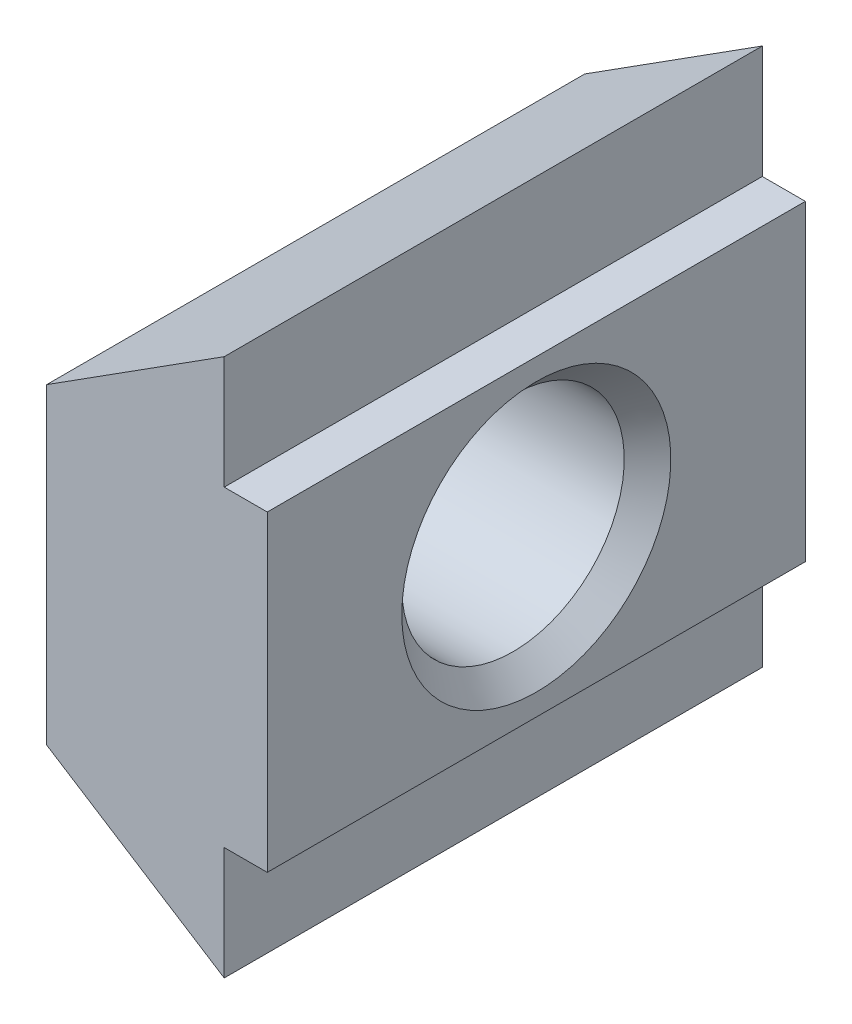
SolidWorks part; units mm, degrees
material "A6061"
ref_plane "前视基准面" through (0, 0, 0) normal (0, 0, 1) x (1, 0, 0)
ref_plane "上视基准面" through (0, 0, 0) normal (0, 1, 0) x (1, 0, 0)
ref_plane "右视基准面" through (0, 0, 0) normal (1, 0, 0) x (0, 0, -1)
sketch "草图1" plane through (0, 0, 0) normal (0, 0, 1) x (1, 0, 0)
  line L0 (-4.1, -2.9) -> (-0.8, -5)
  line L1 (-0.8, -5) -> (-0.8, -2.9)
  line L2 (-0.8, -2.9) -> (0, -2.9)
  line L3 (0, -2.9) -> (0, 2.9)
  line L4 (0, 2.9) -> (-0.8, 2.9)
  line L5 (-0.8, 2.9) -> (-0.8, 5)
  line L6 (-0.8, 5) -> (-4.1, 2.9)
  line L7 (-4.1, 2.9) -> (-4.1, -2.9)
extrude "凸台-拉伸1" add sketch "草图1" against normal blind 5 and the other way blind 5
sketch "草图2" plane through (0, 0, 0) normal (0, 0, 1) x (1, 0, 0)
  line L0 (-4.1, 0) -> (-4.1, 2.5)
  line L1 (-4.1, 2.5) -> (-3.667, 2.067)
  line L2 (-3.667, 2.067) -> (-0.433, 2.067)
  line L3 (-0.433, 2.067) -> (0, 2.5)
  line L4 (0, 2.5) -> (0, 0)
  line L5 (0, 0) -> (-4.1, 0)
  line L6 (0, 0) -> (-4.1, 0) construction
revolve "切除-旋转1" cut sketch "草图2" angle 360 about L6 reverse direction yes
cosmetic thread "装饰螺纹线1" parameters "D1"=4.1, "D2"=5
ref_plane "基准面1" through (-4.1, 0, 0) normal (1, 0, 0) x (0, 0, -1)
ref_plane "基准面2" through (-0.8, 0, 0) normal (1, 0, 0) x (0, 0, -1)
ref_plane "nut XY" through (0, 0, 0) normal (1, 0, 0) x (0, 0, -1)
ref_plane "nut XZ" through (0, 0, 0) normal (0, -1, 0) x (-1, 0, 0)
ref_plane "nut YZ" through (0, 0, 0) normal (0, 0, -1) x (-1, 0, 0)
ref_axis "nut X" through (0, 0, 80.9) along (0, 0, -1)
ref_axis "nut Y" through (0, -50, 0) along (0, 1, 0)
ref_axis "nut Z" through (80.9, 0, 0) along (-1, 0, 0)
sketch3d "nut"
  point P0 (0, 0, 0)
ref_plane "to_bolt XY" through (-4.1, 0, 0) normal (1, 0, 0) x (0, 0, -1)
ref_plane "to_bolt XZ" through (0, 0, 0) normal (0, -1, 0) x (-1, 0, 0)
ref_plane "to_bolt YZ" through (0, 0, 0) normal (0, 0, -1) x (-1, 0, 0)
ref_axis "to_bolt X" through (-4.1, 0, 80.9) along (0, 0, -1)
ref_axis "to_bolt Y" through (-4.1, -50, 0) along (0, 1, 0)
ref_axis "to_bolt Z" through (80.9, 0, 0) along (-1, 0, 0)
sketch3d "to_bolt"
  point P0 (-4.1, 0, 0)
ref_plane "to_frames XY" through (-0.8, 0, 0) normal (1, 0, 0) x (0, 0, -1)
ref_plane "to_frames XZ" through (0, 0, 0) normal (0, -1, 0) x (-1, 0, 0)
ref_plane "to_frames YZ" through (0, 0, 0) normal (0, 0, -1) x (-1, 0, 0)
ref_axis "to_frames X" through (-0.8, 0, 80.9) along (0, 0, -1)
ref_axis "to_frames Y" through (-0.8, -50, 0) along (0, 1, 0)
ref_axis "to_frames Z" through (80.9, 0, 0) along (-1, 0, 0)
sketch3d "to_frames"
  point P0 (-0.8, 0, 0)
